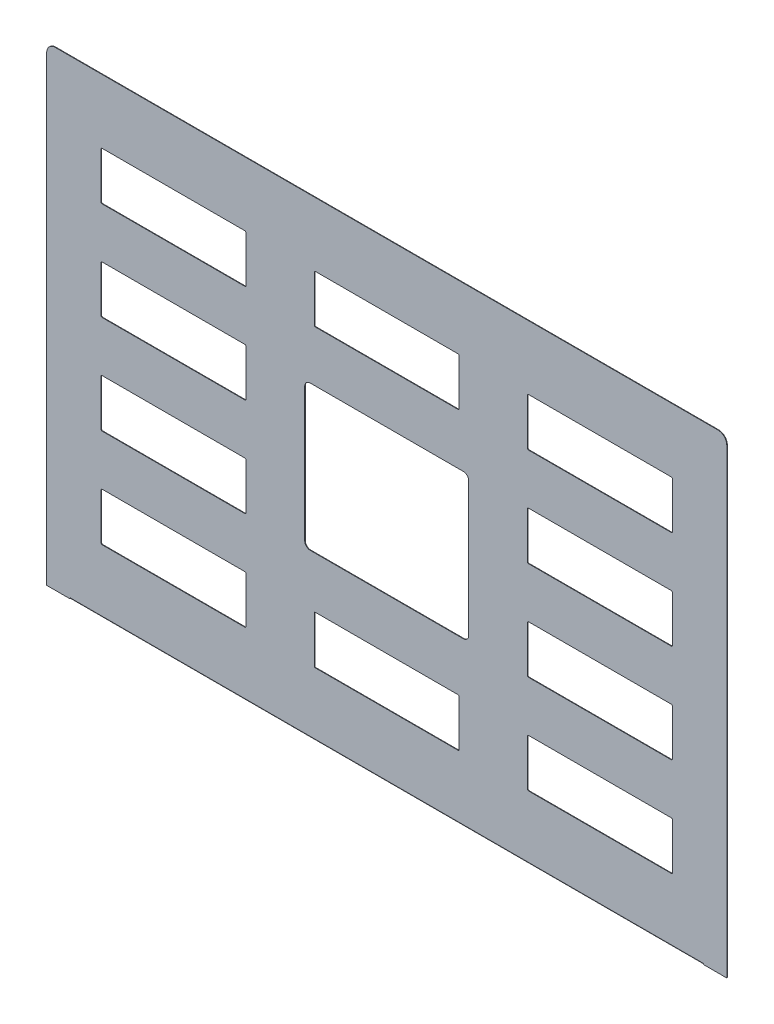
SolidWorks part; units mm, degrees
note: The reader was unsure of these and kept them because the rebuilt part matched: flange length of "Edge-Flange1".
ref_plane "Front Plane" through (0, 0, 0) normal (0, 0, 1) x (1, 0, 0)
ref_plane "Top Plane" through (0, 0, 0) normal (0, 1, 0) x (1, 0, 0)
ref_plane "Right Plane" through (0, 0, 0) normal (1, 0, 0) x (0, 0, -1)
sketch "Sketch1" plane through (0, 0, 0) normal (0, 0, 1) x (1, 0, 0)
  line L1 (0, 0) -> (1244, 0)
  line L2 (0, 0) -> (0, 844)
  line L3 (16, 860) -> (1228, 860)
  line L4 (1244, 0) -> (1244, 844)
  arc A0 (1228, 860) -> (1244, 844) centre (1228, 844) cw
  arc A1 (0, 844) -> (16, 860) centre (16, 844) cw
  dimension "D3" = 16
  dimension "D1" = 1244
  dimension "D2" = 860
base flange "Base-Flange1" sketch "Sketch1" thickness 1 reverse thickness direction no parameters "D1"=1
edge flange "Edge-Flange1" sketch "Sketch8" flange angle 90 flange length 18 flange position material inside bend radius 1 thickness 1 relief rectangular parameters "D6"=10
sketch "Sketch8" plane through (0, 0, -1) normal (0, -1, 0) x (-1, 0, 0)
  line L0 (0, 0) -> (-1244, 0) construction
  line L1 (-43, 0) -> (-1201, 0)
  line L2 (-1201, 0) -> (-1201, 18)
  line L3 (-1201, 18) -> (-43, 18)
  line L4 (-43, 18) -> (-43, 0)
  line L5 (0, 0) -> (0, -1) construction
  line L6 (-1244, 0) -> (-1244, -1) construction
  circle A0 centre (-82, 9) radius 2.75
  circle A1 centre (-262, 9) radius 2.75
  circle A2 centre (-442, 9) radius 2.75
  circle A3 centre (-622, 9) radius 2.75
  circle A4 centre (-802, 9) radius 2.75
  circle A5 centre (-982, 9) radius 2.75
  circle A6 centre (-1162, 9) radius 2.75
  point P6 (-43, 9)
  dimension "D1" = 5.5
  dimension "D2" = 39
  dimension "D4" = 43
  dimension "D5" = 43
  dimension "D3" = 7
bend "EdgeBend1" bend radius 1 bend angle 90 parameters "D5"=1
sketch "Sketch9" plane through (0, 0, 0) normal (0, 0, 1) x (1, 0, 0)
  line L0 (1244, 0) -> (1244, 844) construction
  line L1 (1142.5, 743) -> (881.5, 743)
  line L2 (1144.5, 741) -> (1144.5, 657)
  line L3 (1142.5, 655) -> (881.5, 655)
  line L4 (879.5, 741) -> (879.5, 657)
  line L5 (1228, 860) -> (16, 860) construction
  line L6 (754.5, 741) -> (754.5, 657)
  line L7 (752.5, 743) -> (491.5, 743)
  line L8 (752.5, 655) -> (491.5, 655)
  line L9 (489.5, 741) -> (489.5, 657)
  line L10 (364.5, 741) -> (364.5, 657)
  line L11 (362.5, 743) -> (101.5, 743)
  line L12 (362.5, 655) -> (101.5, 655)
  line L13 (99.5, 741) -> (99.5, 657)
  line L18 (364.5, 561) -> (364.5, 477)
  line L19 (362.5, 563) -> (101.5, 563)
  line L20 (362.5, 475) -> (101.5, 475)
  line L21 (99.5, 561) -> (99.5, 477)
  line L26 (364.5, 381) -> (364.5, 297)
  line L27 (362.5, 383) -> (101.5, 383)
  line L28 (362.5, 295) -> (101.5, 295)
  line L29 (99.5, 381) -> (99.5, 297)
  line L30 (754.5, 201) -> (754.5, 117)
  line L31 (752.5, 203) -> (491.5, 203)
  line L32 (752.5, 115) -> (491.5, 115)
  line L33 (489.5, 201) -> (489.5, 117)
  line L34 (364.5, 201) -> (364.5, 117)
  line L35 (362.5, 203) -> (101.5, 203)
  line L36 (362.5, 115) -> (101.5, 115)
  line L37 (99.5, 201) -> (99.5, 117)
  line L38 (1144.5, 561) -> (1144.5, 477)
  line L39 (1142.5, 563) -> (881.5, 563)
  line L40 (1142.5, 475) -> (881.5, 475)
  line L41 (879.5, 561) -> (879.5, 477)
  line L42 (1144.5, 381) -> (1144.5, 297)
  line L43 (1142.5, 383) -> (881.5, 383)
  line L44 (1142.5, 295) -> (881.5, 295)
  line L45 (879.5, 381) -> (879.5, 297)
  line L46 (1144.5, 201) -> (1144.5, 117)
  line L47 (1142.5, 203) -> (881.5, 203)
  line L48 (1142.5, 115) -> (881.5, 115)
  line L49 (879.5, 201) -> (879.5, 117)
  line L50 (754.5, 381) -> (754.5, 297) [skipped]
  line L51 (754.5, 561) -> (754.5, 477) [skipped]
  line L52 (752.5, 563) -> (491.5, 563) [skipped]
  line L53 (752.5, 475) -> (491.5, 475) [skipped]
  line L54 (489.5, 561) -> (489.5, 477) [skipped]
  line L55 (752.5, 383) -> (491.5, 383) [skipped]
  line L56 (752.5, 295) -> (491.5, 295) [skipped]
  line L57 (489.5, 381) -> (489.5, 297) [skipped]
  arc A0 (1144.5, 657) -> (1142.5, 655) centre (1142.5, 657) cw
  arc A1 (881.5, 655) -> (879.5, 657) centre (881.5, 657) cw
  arc A2 (881.5, 743) -> (879.5, 741) centre (881.5, 741) ccw
  arc A3 (1142.5, 743) -> (1144.5, 741) centre (1142.5, 741) cw
  arc A4 (752.5, 743) -> (754.5, 741) centre (752.5, 741) cw
  arc A5 (754.5, 657) -> (752.5, 655) centre (752.5, 657) cw
  arc A6 (491.5, 655) -> (489.5, 657) centre (491.5, 657) cw
  arc A7 (491.5, 743) -> (489.5, 741) centre (491.5, 741) ccw
  arc A8 (362.5, 743) -> (364.5, 741) centre (362.5, 741) cw
  arc A9 (364.5, 657) -> (362.5, 655) centre (362.5, 657) cw
  arc A10 (101.5, 655) -> (99.5, 657) centre (101.5, 657) cw
  arc A11 (101.5, 743) -> (99.5, 741) centre (101.5, 741) ccw
  arc A16 (362.5, 563) -> (364.5, 561) centre (362.5, 561) cw
  arc A17 (364.5, 477) -> (362.5, 475) centre (362.5, 477) cw
  arc A18 (101.5, 475) -> (99.5, 477) centre (101.5, 477) cw
  arc A19 (101.5, 563) -> (99.5, 561) centre (101.5, 561) ccw
  arc A24 (362.5, 383) -> (364.5, 381) centre (362.5, 381) cw
  arc A25 (364.5, 297) -> (362.5, 295) centre (362.5, 297) cw
  arc A26 (101.5, 295) -> (99.5, 297) centre (101.5, 297) cw
  arc A27 (101.5, 383) -> (99.5, 381) centre (101.5, 381) ccw
  arc A28 (752.5, 203) -> (754.5, 201) centre (752.5, 201) cw
  arc A29 (754.5, 117) -> (752.5, 115) centre (752.5, 117) cw
  arc A30 (491.5, 115) -> (489.5, 117) centre (491.5, 117) cw
  arc A31 (491.5, 203) -> (489.5, 201) centre (491.5, 201) ccw
  arc A32 (362.5, 203) -> (364.5, 201) centre (362.5, 201) cw
  arc A33 (364.5, 117) -> (362.5, 115) centre (362.5, 117) cw
  arc A34 (101.5, 115) -> (99.5, 117) centre (101.5, 117) cw
  arc A35 (101.5, 203) -> (99.5, 201) centre (101.5, 201) ccw
  arc A36 (1142.5, 563) -> (1144.5, 561) centre (1142.5, 561) cw
  arc A37 (1144.5, 477) -> (1142.5, 475) centre (1142.5, 477) cw
  arc A38 (881.5, 475) -> (879.5, 477) centre (881.5, 477) cw
  arc A39 (881.5, 563) -> (879.5, 561) centre (881.5, 561) ccw
  arc A40 (1142.5, 383) -> (1144.5, 381) centre (1142.5, 381) cw
  arc A41 (1144.5, 297) -> (1142.5, 295) centre (1142.5, 297) cw
  arc A42 (881.5, 295) -> (879.5, 297) centre (881.5, 297) cw
  arc A43 (881.5, 383) -> (879.5, 381) centre (881.5, 381) ccw
  arc A44 (1142.5, 203) -> (1144.5, 201) centre (1142.5, 201) cw
  arc A45 (1144.5, 117) -> (1142.5, 115) centre (1142.5, 117) cw
  arc A46 (881.5, 115) -> (879.5, 117) centre (881.5, 117) cw
  arc A47 (881.5, 203) -> (879.5, 201) centre (881.5, 201) ccw
  arc A48 (754.5, 477) -> (752.5, 475) centre (752.5, 477) cw [skipped]
  arc A49 (491.5, 475) -> (489.5, 477) centre (491.5, 477) cw [skipped]
  arc A50 (752.5, 383) -> (754.5, 381) centre (752.5, 381) cw [skipped]
  arc A51 (754.5, 297) -> (752.5, 295) centre (752.5, 297) cw [skipped]
  arc A52 (491.5, 295) -> (489.5, 297) centre (491.5, 297) cw [skipped]
  arc A53 (491.5, 383) -> (489.5, 381) centre (491.5, 381) ccw [skipped]
  arc A54 (752.5, 563) -> (754.5, 561) centre (752.5, 561) cw [skipped]
  arc A55 (491.5, 563) -> (489.5, 561) centre (491.5, 561) ccw [skipped]
  dimension "D5" = 2
  dimension "D1" = 99.5
  dimension "D2" = 265
  dimension "D3" = 88
  dimension "D4" = 117
  dimension "D6" = 3
  dimension "D7" = 4
extrude "Cut-Extrude1" cut sketch "Sketch9" against normal blind 10 normal cut yes
sketch "Sketch10" plane through (0, 0, 0) normal (0, 0, 1) x (1, 0, 0)
  line L1 (482, 296.5) -> (762, 296.5)
  line L2 (472, 306.5) -> (472, 551.5)
  line L3 (482, 561.5) -> (762, 561.5)
  line L4 (772, 306.5) -> (772, 551.5)
  line L8 (1228, 860) -> (16, 860) construction
  arc A0 (482, 296.5) -> (472, 306.5) centre (482, 306.5) cw
  arc A1 (762, 296.5) -> (772, 306.5) centre (762, 306.5) ccw
  arc A2 (472, 551.5) -> (482, 561.5) centre (482, 551.5) cw
  arc A3 (762, 561.5) -> (772, 551.5) centre (762, 551.5) cw
  point P8 (622, 561.5)
  point P9 (622, 860)
  dimension "D5" = 10
  dimension "D1" = 300
  dimension "D2" = 265
  dimension "D3" = 298.5
extrude "Cut-Extrude2" cut sketch "Sketch10" against normal blind 10 normal cut yes
sketch "Sketch11" plane through (0, 0, -1) normal (0, 0, -1) x (-1, 0, 0)
  line L0 (-762.2929, 578.3623) -> (-474.7071, 578.3623) construction
  line L1 (-762.2929, 578.3623) -> (-474.7071, 578.3623) construction
  line L2 (-455.5, 559.4244) -> (-455.5, 302.3841) construction
  line L3 (-474.7071, 282.858) -> (-762.2929, 282.858) construction
  line L4 (-781.5, 302.8243) -> (-781.5, 559.4244) construction
  line L5 (-781.5, 302.3841) -> (-781.5, 559.4244) construction
  ellipse E0 centre (-474.7071, 576.3964) end of major axis (-472.7071, 576.3964) minor radius 1.9659 (-472.7071, 576.3964) -> (-474.7071, 578.3623) ccw construction
sketch "Bend-Lines1" [suppressed] plane through (0, 0, 0) normal (0, 1, 0) x (1, 0, 0)
sketch "Bounding-Box1" [suppressed] plane through (0, 0, 0) normal (0, 1, 0) x (1, 0, 0)
sheet metal parameters "Sheet-Metal1" thickness 1 parameters "D1"=2
flat pattern "Flat-Pattern1" [suppressed]
sketch "Bend-Lines2" plane through (0, 0, 0) normal (0, 1, 0) x (1, 0, 0)
sketch3d "Bounding-Box2" [suppressed]
  line L0 (15, 15, 0) -> (-1227, 15, 0) construction
  line L1 (15, -935, 0) -> (-1227, -935, 0) construction
  line L2 (15, 15, 0) -> (15, -935, 0) construction
  line L3 (-1227, 15, 0) -> (-1227, -935, 0) construction
sheet metal parameters "Sheet-Metal2" thickness 1 parameters "D1"=2
flat pattern "Flat-Pattern1"
sketch "Bend-Lines2" plane through (0, 0, 0) normal (0, 0, 1) x (1, 0, 0)
  line L0 (0, 0.8219) -> (1242, 0.8219) construction
  line L1 (0, 0.8219) -> (1242, 0.8219) construction
sketch3d "Bounding-Box2" [suppressed]
  line L0 (-15, 15, 0) -> (1227, 15, 0) construction
  line L1 (-15, -946.3562, 0) -> (1227, -946.3562, 0) construction
  line L2 (-15, 15, 0) -> (-15, -946.3562, 0) construction
  line L3 (1227, 15, 0) -> (1227, -946.3562, 0) construction
bend of the flat pattern "Flatten-<EdgeBend1>1"
sheet metal parameters "Sheet-Metal3" thickness 1 parameters "D1"=2
flat pattern "Flat-Pattern1"
sketch "Bend-Lines2" plane through (0, 0, 0) normal (0, 0, 1) x (1, 0, 0)
  line L0 (0, 0.8219) -> (1244, 0.8219) construction
  line L1 (0, 0.8219) -> (1244, 0.8219) construction
sketch3d "Bounding-Box2" [suppressed]
  line L0 (-16, 16, 0) -> (1228, 16, 0) construction
  line L1 (-16, -945.3562, 0) -> (1228, -945.3562, 0) construction
  line L2 (-16, 16, 0) -> (-16, -945.3562, 0) construction
  line L3 (1228, 16, 0) -> (1228, -945.3562, 0) construction
bend of the flat pattern "Flatten-<EdgeBend1>1"
sheet metal parameters "Sheet-Metal4" thickness 1 parameters "D1"=2
flat pattern "Flat-Pattern1"
sketch "Bend-Lines2" plane through (0, 0, 0) normal (0, 0, 1) x (1, 0, 0)
  line L0 (43, 0.8219) -> (1201, 0.8219) construction
  line L1 (43, 0.8219) -> (1201, 0.8219) construction
sketch3d "Bounding-Box2" [suppressed]
  line L0 (-16, 16, 0) -> (1228, 16, 0) construction
  line L1 (-16, -861.3562, 0) -> (1228, -861.3562, 0) construction
  line L2 (-16, 16, 0) -> (-16, -861.3562, 0) construction
  line L3 (1228, 16, 0) -> (1228, -861.3562, 0) construction
bend of the flat pattern "Flatten-<EdgeBend1>1"
equation "\"D5@Sketch8\"=\"D4@Sketch8\""
